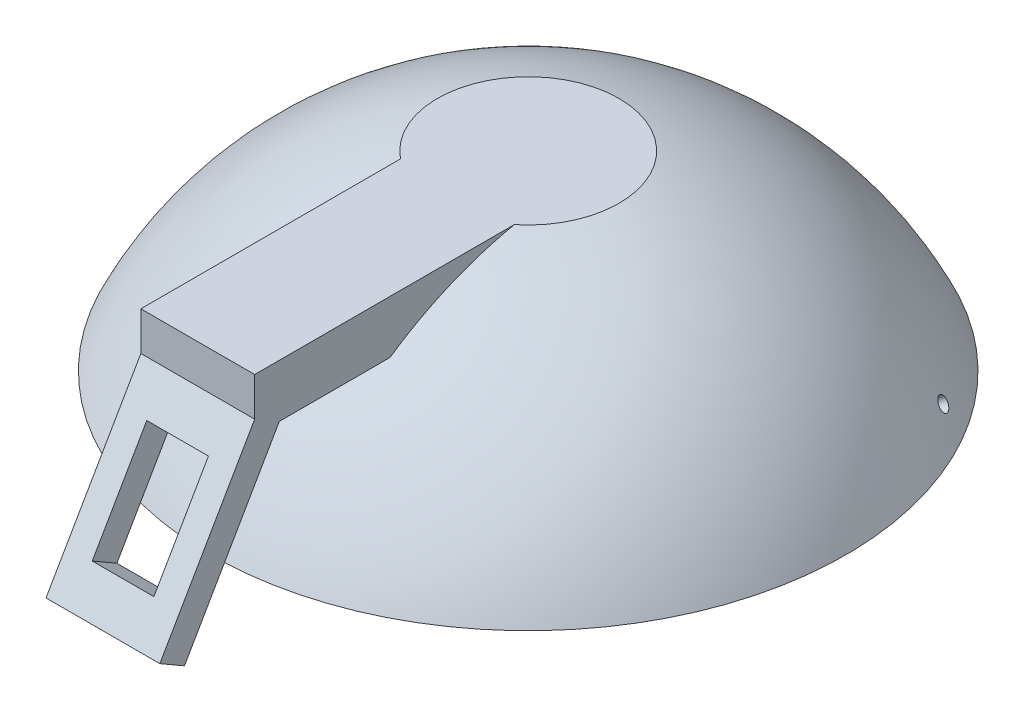
SolidWorks part; units mm, degrees
ref_plane "前视基准面" through (0, 0, 0) normal (0, 0, 1) x (1, 0, 0)
ref_plane "上视基准面" through (0, 0, 0) normal (0, 1, 0) x (1, 0, 0)
ref_plane "右视基准面" through (0, 0, 0) normal (1, 0, 0) x (0, 0, -1)
sketch "草图1" plane through (0, 0, 0) normal (0, 0, 1) x (1, 0, 0)
  line L0 (0, 0) -> (0, 62) construction
  line L1 (0, 0) -> (64.0859, 37) construction
  line L2 (0, 0) -> (67.0668, 31.2738) construction
  line L3 (0, 0) -> (19.1526, 71.4785) construction
  line L4 (19.1526, 71.4785) -> (0, 71.4785)
  line L5 (0, 71.4785) -> (0, 67.4785)
  line L6 (0, 67.4785) -> (18.6186, 67.4785)
  line L7 (67.0668, 31.2738) -> (63.4415, 29.5833)
  arc A0 (67.0668, 31.2738) -> (19.1526, 71.4785) centre (0, 0) ccw
  arc A1 (63.4415, 29.5833) -> (18.6186, 67.4785) centre (0, 0) ccw
  dimension "D1" = 60
  dimension "D4" = 70
  dimension "D5" = 74
  dimension "D2" = 45
  dimension "D3" = 5
  dimension "D6" = 4
revolve "旋转1" add sketch "草图1" angle 360 about L0
ref_axis "基准轴1" through (73.7735, 0, 0) along (-1, 0, 0)
ref_plane "基准面2" through (0, 0, 0) normal (0, 0.5, 0.866) x (-1, 0, 0)
sketch "草图3" plane through (0, 0, 0) normal (0, 0.5, 0.866) x (-1, 0, 0)
  circle A0 centre (0, 0) radius 1.5
extrude "切除-拉伸2" cut sketch "草图3" along normal through all
pattern_circular "阵列(圆周)2" count 3 over 360 about axis through (0, 71.4785, 0) along (0, -1, 0) of "切除-拉伸2"
ref_axis "基准轴2" through (0, 0, 73.7735) along (0, 0, -1)
ref_plane "基准面3" through (0, 43, 74.4782) normal (0, 0.5, 0.866) x (-1, 0, 0)
sketch "草图4" plane through (0, 43, 74.4782) normal (0, 0.5, 0.866) x (-1, 0, 0)
  line L1 (-6.5, -11.5) -> (6.5, -11.5)
  line L2 (-6.5, -11.5) -> (-6.5, 11.5)
  line L3 (-6.5, 11.5) -> (6.5, 11.5)
  line L4 (6.5, -11.5) -> (6.5, 11.5)
  line L5 (-6.5, -11.5) -> (6.5, 11.5) construction
  line L6 (-6.5, 11.5) -> (6.5, -11.5) construction
  line L7 (-12, -20) -> (12, -20)
  line L8 (-12, -20) -> (-12, 20)
  line L9 (-12, 20) -> (12, 20)
  line L10 (12, -20) -> (12, 20)
  line L11 (-12, -20) -> (12, 20) construction
  line L12 (-12, 20) -> (12, -20) construction
  point P0 (0, 0)
  point P6 (0, 0)
  dimension "D1" = 13
  dimension "D2" = 23
  dimension "D3" = 40
  dimension "D4" = 24
extrude "凸台-拉伸1" add sketch "草图4" along normal blind 6 separate body
sketch "草图5" plane through (0, 71.4785, 0) normal (0, 1, 0) x (1, 0, 0)
  line L4 (12, -64.4782) -> (-12, -64.4782)
  line L5 (-12, -64.4782) -> (-12, -69.6743)
  line L6 (-12, -69.6743) -> (12, -69.6743)
  line L7 (12, -69.6743) -> (12, -64.4782)
  line L8 (12, -64.4782) -> (-12, -64.4782)
  line L9 (-12, -64.4782) -> (-12, -69.6743)
  line L10 (-12, -69.6743) -> (12, -69.6743)
  line L11 (12, -69.6743) -> (12, -64.4782)
  dimension "D1" = 0
extrude "凸台-拉伸2" add sketch "草图5" against normal up to next
sketch "草图8" plane through (0, 0, 64.4782) normal (0, 0, -1) x (-1, 0, 0)
  line L4 (-12, 71.4785) -> (-12, 60.3205)
  line L5 (-12, 60.3205) -> (12, 60.3205)
  line L6 (12, 60.3205) -> (12, 71.4785)
  line L7 (12, 71.4785) -> (-12, 71.4785)
  line L8 (-12, 71.4785) -> (-12, 60.3205)
  line L9 (-12, 60.3205) -> (12, 60.3205)
  line L10 (12, 60.3205) -> (12, 71.4785)
  line L11 (12, 71.4785) -> (-12, 71.4785)
  dimension "D1" = 0
extrude "凸台-拉伸3" add sketch "草图8" along normal up to next
